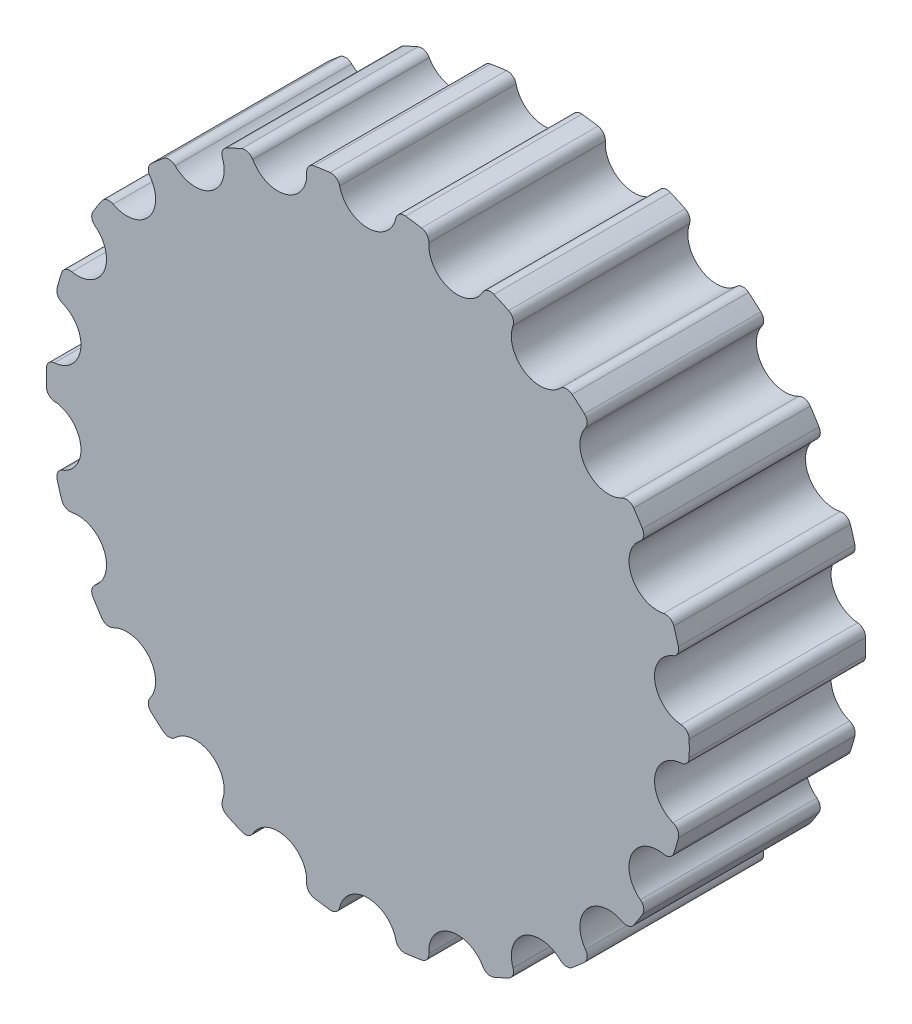
SolidWorks part; units mm, degrees
ref_plane "Front Plane" through (0, 0, 0) normal (0, 0, 1) x (1, 0, 0)
ref_plane "Top Plane" through (0, 0, 0) normal (0, 1, 0) x (1, 0, 0)
ref_plane "Right Plane" through (0, 0, 0) normal (1, 0, 0) x (0, 0, -1)
sketch "Sketch1" plane through (0, 0, 0) normal (0, 0, 1) x (1, 0, 0)
  line L0 (0, 27.1013) -> (0, 0) construction
  circle A0 centre (0, 0) radius 27.3255
  circle A1 centre (0, 0) radius 28.0113 construction
  circle A2 centre (0, 27.1013) radius 2.45
  circle A3 centre (3.1203, 26.3916) radius 0.75
  circle A4 centre (-3.1203, 26.3916) radius 0.75
  circle A5 centre (0, 0) radius 24.6513
  dimension "D1" = 56.0225
  dimension "D2" = 54.6509
  dimension "D3" = 2.45
  dimension "D5" = 0.75
  dimension "D6" = 49.3025
extrude "Boss-Extrude1" add sketch "Sketch1" along normal mid plane 15 contours A0
extrude "Cut-Extrude1" cut sketch "Sketch1<3>" against normal mid plane 15 contours A0 A2 | A4 A2 A0 | A3 A0 A2 region at (2.6203, 27.0501, 0) region at (-2.6203, 27.0501, 0) region at (0, 26.1624, 0)
sketch "Sketch1<3>" plane through (0, 0, 0) normal (0, 0, 1) x (1, 0, 0) same geometry as "Sketch1"
pattern_circular "CirPattern1" count 22 over 360 about axis through (0, 0, 7.5) along (0, 0, 1) of "Cut-Extrude1"
equation "\"PITCH\"= 8'HTD "
equation "\"NO OF TEETH\"= 22"
equation "\"U\"= .027in"
equation "\"WIDTH\"= 15"
equation "\"PITCH CIRCLE DIA\"= \"PITCH\" * \"NO OF TEETH\" / 3.1415926535897932384626433832795"
equation "\"OD\"= \"PITCH CIRCLE DIA\" - \"U\" * 2"
equation "\"RADIUS\"= .86"
equation "\"D1@Sketch1\"=\"PITCH CIRCLE DIA\""
equation "\"D2@Sketch1\"=\"OD\""
equation "\"ANGLE\"= 360 / \"NO OF TEETH\""
equation "\"PROFILE RADIUS\"= 2.45"
equation "\"FILLET RADIUS\"= .75"
equation "\"B\"= 3.36'\"LENGTH FROM PITCH LINE TO BOTTOM\""
equation "\"INNER DIA\"= \"PITCH CIRCLE DIA\" - \"B\" * 2"
equation "\"D6@Sketch1\"=\"INNER DIA\""
equation "\"D1@Boss-Extrude1\"=\"WIDTH\""
equation "\"D1@CirPattern1\"=\"NO OF TEETH\""
